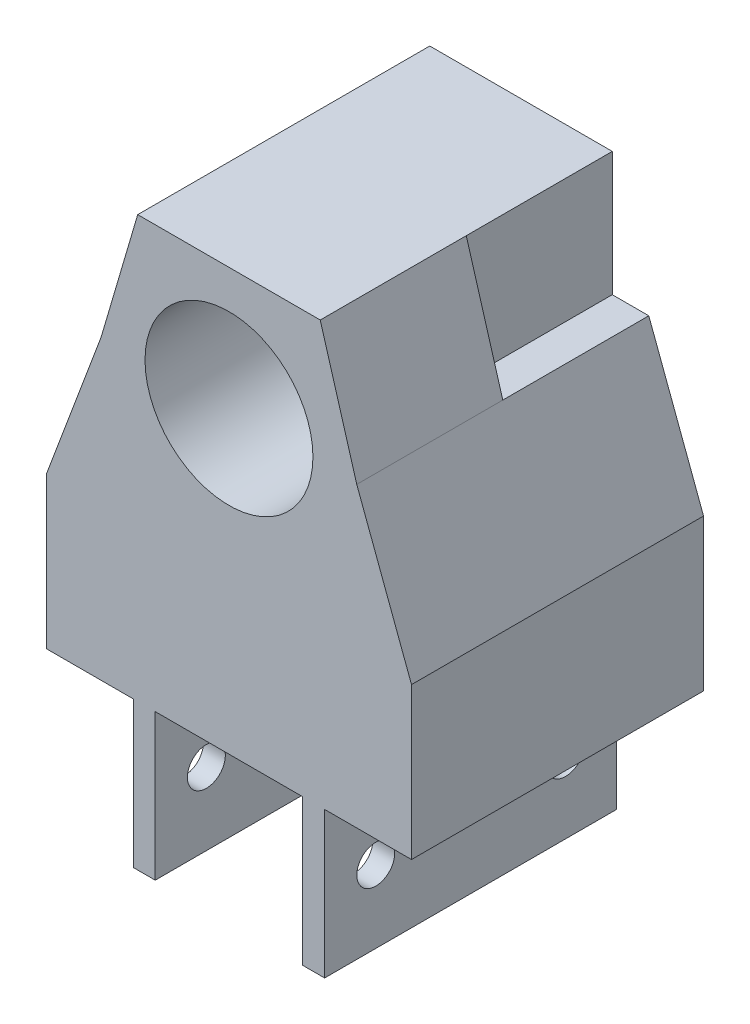
SolidWorks part; units mm, degrees
ref_plane "前视基准面" through (0, 0, 0) normal (0, 0, 1) x (1, 0, 0)
ref_plane "上视基准面" through (0, 0, 0) normal (0, 1, 0) x (1, 0, 0)
ref_plane "右视基准面" through (0, 0, 0) normal (1, 0, 0) x (0, 0, -1)
other "Configuration Table"
sketch "草图1" plane through (0, 0, 0) normal (0, 0, 1) x (1, 0, 0)
  line L0 (0, -39.6057) -> (0, 25.2485) construction
  line L9 (10.1, -25.375) -> (13.1, -25.375)
  line L10 (-25, -5.375) -> (-13.1, -5.375)
  line L11 (-25, -5.375) -> (-25, 5.375)
  line L12 (-25, 5.375) -> (25, 5.375)
  line L13 (25, -5.375) -> (25, 5.375)
  line L14 (-25, -5.375) -> (25, 5.375) construction
  line L15 (-25, 5.375) -> (25, -5.375) construction
  line L16 (-10.1, -5.375) -> (10.1, -5.375)
  line L17 (-13.1, -5.375) -> (-13.1, -25.375)
  line L18 (-13.1, -25.375) -> (-10.1, -25.375)
  line L19 (13.1, -5.375) -> (13.1, -25.375)
  line L21 (-10.1, -25.375) -> (-10.1, -5.375)
  line L22 (-10.1, -5.375) -> (10.1, -5.375)
  line L23 (10.1, -25.375) -> (10.1, -5.375)
  line L24 (-8.4435, -45.2703) -> (10.1, -5.375) construction
  line L25 (-10.1, -5.375) -> (10.5079, -49.7116) construction
  line L26 (-10.1, -5.375) -> (10.1, -5.375)
  line L27 (13.1, -5.375) -> (25, -5.375)
  point P2 (0, 0)
  point P12 (0, -27.1045)
  dimension "D1" = 50
  dimension "D2" = 10.75
  dimension "D3" = 20
  dimension "D4" = 3
  dimension "D5" = 20.2
extrude "凸台-拉伸1" add sketch "草图1" along normal blind 40 contours L19 L27 L13 L12 L11 L10 L17 L18 L21 L16 L23 L9 region at (0, -2.8061, 0)
sketch "草图2" plane through (0, 0, 0) normal (0, 0, -1) x (-1, 0, 0)
  line L0 (0, -5.375) -> (0, 67.3086) construction
  line L1 (10.1, -5.375) -> (-10.1, -5.375) construction
  line L2 (25, 5.375) -> (-25, 5.375) construction
  line L3 (-12.5, 5.375) -> (12.5, 5.375)
  line L4 (-12.5, 5.375) -> (-12.5, 52.375)
  line L5 (-12.5, 52.375) -> (12.5, 52.375)
  line L6 (12.5, 5.375) -> (12.5, 52.375)
  line M14 (25, 5.375) -> (-25, 5.375)
  dimension "D1" = 47
  dimension "D2" = 25
extrude "凸台-拉伸2" add sketch "草图2" against normal up to surface (40 mm away) contours L6 L5 L4 M14 | L4 L3 L6 L5 region at (0, 28.875, 0) up to face at (0, -10.25, 40)
hole_wizard "孔3" positions "草图9" profile "草图8" legacy end condition through all
sketch "草图9" plane through (0, 0, 40) normal (0, 0, 1) x (1, 0, 0)
  line L0 (0, -5.375) -> (0, 52.375) construction
  line L1 (-10.1, -5.375) -> (10.1, -5.375) construction
  line L2 (12.5, 52.375) -> (-12.5, 52.375) construction
  line L4 (12.5, 5.375) -> (25, 5.375) construction
  point P0 (0, 35.625)
  dimension "D1" = 30.25
sketch "草图8" plane through (0, 35.625, 40) normal (1, 0, 0) x (0, -1, 0)
  line L0 (0, 0) -> (0, 40)
  line L1 (0, 40) -> (11.5, 40)
  line L2 (11.5, 40) -> (11.5, 0)
  line L3 (11.5, 0) -> (0, 0)
  line L4 (0, 110) -> (0, -10) construction
  dimension "直径" = 23
  dimension "深度" = 40
sketch "草图10" plane through (0, 0, 40) normal (0, 0, 1) x (1, 0, 0)
  line L0 (12.5, 35.375) -> (17.5, 35.375)
  line L1 (12.5, 5.375) -> (12.5, 52.375) construction
  line L2 (17.5, 35.375) -> (25, 15.375)
  line L3 (25, 15.375) -> (25, 5.375)
  line L4 (12.5, 35.375) -> (12.5, 5.375)
  line L5 (12.5, 5.375) -> (25, 5.375)
  line L6 (0, 52.375) -> (0, -5.375) construction
  line L7 (12.5, 52.375) -> (-12.5, 52.375) construction
  line L8 (-10.1, -5.375) -> (10.1, -5.375) construction
  line L9 (-12.5, 35.375) -> (-12.5, 5.375)
  line L10 (-12.5, 35.375) -> (-17.5, 35.375)
  line L11 (-17.5, 35.375) -> (-25, 15.375)
  line L12 (-25, 15.375) -> (-25, 5.375)
  line L13 (-12.5, 5.375) -> (-25, 5.375)
  dimension "D1" = 30
  dimension "D2" = 5
  dimension "D3" = 10
extrude "凸台-拉伸3" add sketch "草图10" against normal up to surface (40 mm away) up to face at (11.5, 35.625, 0)
sketch "草图12" plane through (0, 0, 40) normal (0, 0, 1) x (1, 0, 0)
  line L0 (12.5, 52.375) -> (17.5, 35.375)
  line L1 (25, 15.375) -> (17.5, 35.375) construction
  line L2 (17.5, 35.375) -> (12.5, 35.375)
  line L3 (12.5, 35.375) -> (12.5, 52.375)
  line L4 (-12.5, 52.375) -> (-17.5, 35.375)
  line L5 (-17.5, 35.375) -> (-12.5, 35.375)
  line L6 (-12.5, 35.375) -> (-12.5, 52.375)
extrude "凸台-拉伸5" add sketch "草图12" against normal blind 20
hole_wizard "孔4" positions "草图13" profile "草图14" legacy end condition through all
sketch "草图13" plane through (13.1, 0, 0) normal (1, 0, 0) x (0, 0, -1)
  line L0 (-40, -5.375) -> (0, -5.375) construction
  line L4 (0, -5.375) -> (0, -25.375) construction
  line L5 (-40, -5.375) -> (-40, -25.375) construction
  point P0 (-33, -15.375)
  point P2 (-7, -15.375)
  dimension "D1" = 10
  dimension "D2" = 10
  dimension "D3" = 7
  dimension "D4" = 7
sketch "草图14" plane through (13.1, -15.375, 33) normal (0, 1, 0) x (0, 0, -1)
  line L0 (0, 0) -> (0, 38.1)
  line L1 (0, 38.1) -> (2.6, 38.1)
  line L2 (2.6, 38.1) -> (2.6, 0)
  line L3 (2.6, 0) -> (0, 0)
  line L4 (0, 110) -> (0, -10) construction
  dimension "直径" = 5.2
  dimension "深度" = 38.1
